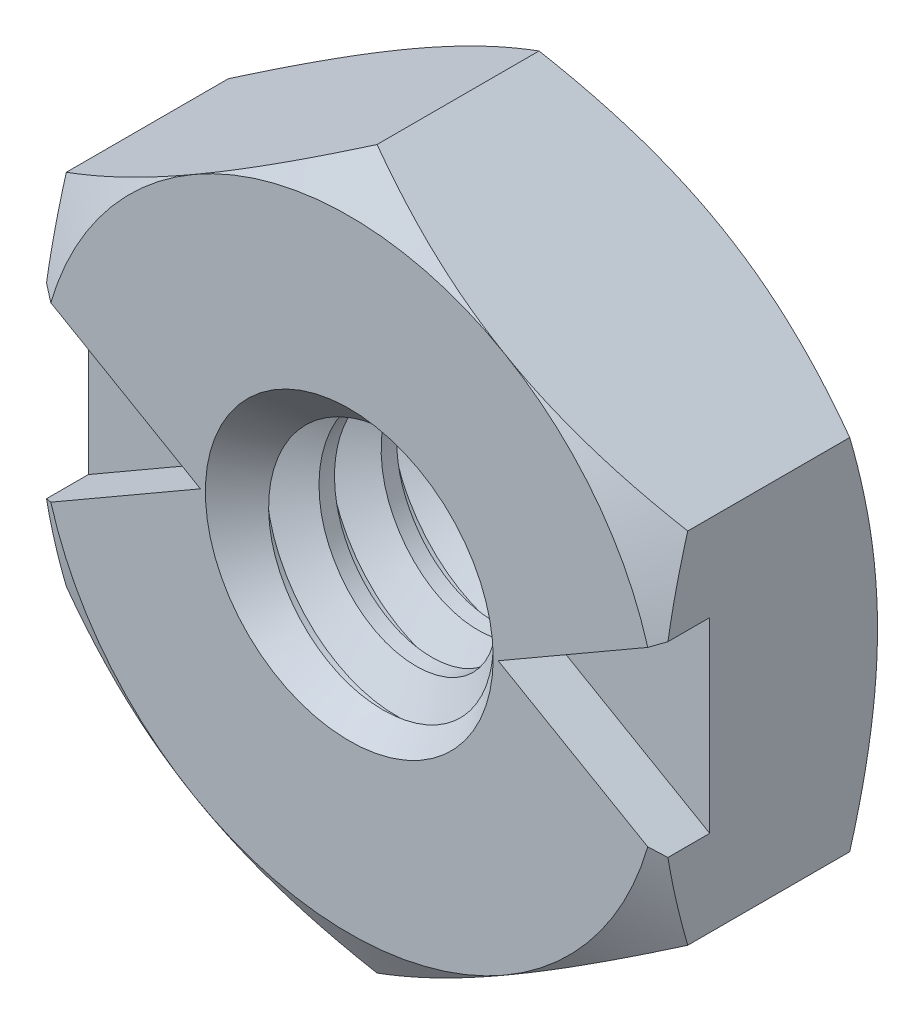
SolidWorks part; units mm, degrees
ref_plane "Front Plane" through (0, 0, 0) normal (0, 0, 1) x (1, 0, 0)
ref_plane "Top Plane" through (0, 0, 0) normal (0, 1, 0) x (1, 0, 0)
ref_plane "Right Plane" through (0, 0, 0) normal (1, 0, 0) x (0, 0, -1)
sketch "Sketch1" plane through (0, 0, 0) normal (0, 0, 1) x (1, 0, 0)
  line L1 (0, 4.5827) -> (-3.9688, 2.2914)
  line L2 (-3.9688, 2.2914) -> (-3.9688, -2.2914)
  line L3 (-3.9688, -2.2914) -> (0, -4.5827)
  line L4 (0, -4.5827) -> (3.9688, -2.2914)
  line L5 (3.9688, -2.2914) -> (3.9687, 2.2914)
  line L6 (3.9687, 2.2914) -> (0, 4.5827)
  circle A0 centre (0, 0) radius 3.9688 construction
  dimension "Hex" = 7.9375
extrude "Extrude1" add sketch "Sketch1" along normal blind 2.7781
sketch "Sketch2" plane through (0, 0, 2.7781) normal (0, 0, -1) x (-1, 0, 0)
  circle A0 centre (0, 0) radius 3.9688 construction
  circle A1 centre (0, 0) radius 3.9688
extrude "Cut-Extrude1" cut sketch "Sketch2" along normal through all draft 60 flip side to cut
sketch "Sketch3" plane through (0, 0, 0) normal (0, 0, 1) x (1, 0, 0)
  circle A1 centre (0, 0) radius 3.9688
  circle A2 centre (0, 0) radius 3.9688
  dimension "D1" = 0
extrude "Cut-Extrude2" cut sketch "Sketch3" along normal through all draft 60 flip side to cut
sketch "Sketch4" plane through (0, 0, 0) normal (0, 0, -1) x (-1, 0, 0)
  circle A0 centre (0, 0) radius 1.7526
  dimension "Thread Dia" = 3.5052
extrude "Cut-Extrude3" cut sketch "Sketch4" against normal through all
sketch "Sketch5" plane through (0, 0, 2.7781) normal (0, 0, -1) x (-1, 0, 0)
  circle A0 centre (0, 0) radius 1.7526 construction
  circle A1 centre (0, 0) radius 1.7526
  point P3 (0, 1.7526)
curve "Helix/Spiral1" pitch 0.7937 height 3.5719 turns 4.5 parameters "pitch"=0.7937
sketch "Sketch6" plane through (0, 0, 0) normal (1, 0, 0) x (0, 0, -1)
  line L0 (-3.5223, 1.8385) -> (-2.7285, 1.8385) construction
  line L1 (-2.7285, 1.8385) -> (-3.1254, 1.1511) construction
  line L2 (-3.1254, 1.1511) -> (-3.5223, 1.8385) construction
  line L3 (-3.175, 1.237) -> (-3.0758, 1.237) construction
  line L4 (-3.4727, 1.7526) -> (-2.7781, 1.7526) construction
  line L5 (-3.1254, 1.1511) -> (-3.1254, 1.237) construction
  line L7 (-3.1254, 1.7526) -> (-3.1254, 1.8385) construction
  line L8 (-3.4975, 1.7956) -> (-3.2246, 1.323)
  line L9 (-3.2246, 1.323) -> (-3.0262, 1.323)
  line L10 (-3.0262, 1.323) -> (-2.7533, 1.7956)
  line L11 (-2.7533, 1.7956) -> (-3.4975, 1.7956)
  line L12 (-3.1254, 1.237) -> (-3.1254, 1.323) construction
  point P18 (-3.1254, 1.7956)
  dimension "D1" = 0.7937
  dimension "D2" = 0.0992
sweep "Sweep1" add profiles "Sketch6" path "Helix/Spiral1"
sketch "Sketch7" plane through (0, 0, 0) normal (0, 0, -1) x (-1, 0, 0)
  circle A0 centre (0, 0) radius 1.8385
extrude "Cut-Extrude4" cut sketch "Sketch7" against normal through all draft 45 and the other way through all
sketch "Sketch8" plane through (0, 0, 2.7781) normal (0, 0, 1) x (1, 0, 0)
  line L0 (0, 0) -> (-1.5922, 0.9193) construction
  circle A1 centre (0, 0) radius 1.8385
  circle A2 centre (0, 0) radius 1.8385
  dimension "D1" = 0
extrude "Cut-Extrude5" cut sketch "Sketch8" against normal through all draft 45 and the other way through all
sketch "Sketch9" plane through (0, 0, 2.7781) normal (0, 0, 1) x (1, 0, 0)
  line L0 (0, 0) -> (-1.8385, 0) construction
  line L1 (0, 4.5827) -> (0, 0) construction
  line L2 (-1.902, 0) -> (-3.9688, 1.1932)
  line L3 (-3.9688, 1.1932) -> (-3.9688, -1.1932)
  line L4 (-3.9688, -1.1932) -> (-1.902, 0)
  line L5 (3.9688, -1.1932) -> (1.902, 0)
  line L6 (3.9688, 1.1932) -> (3.9688, -1.1932)
  line L7 (1.902, 0) -> (3.9688, 1.1932)
  line L8 (-1.8385, 0) -> (-1.902, 0) construction
  line L9 (-3.9688, 0) -> (-1.902, 0) construction
  circle A0 centre (0, 0) radius 1.8385 construction
  circle A1 centre (0, 0) radius 1.8385 construction
  circle A3 centre (0, 0) radius 3.9688 construction
  dimension "D2" = 0.0635
  dimension "D1" = 60
extrude "Cut-Extrude6" cut sketch "Sketch9" against normal blind 0.635
equation "\"D3@Helix/Spiral1\" = \"pitch@Helix/Spiral1\"+\"Height@Extrude1\""
equation "\"D1@Sketch6\" = \"pitch@Helix/Spiral1\""
equation "\"D2@Sketch6\" = \"pitch@Helix/Spiral1\" * 1/8"
